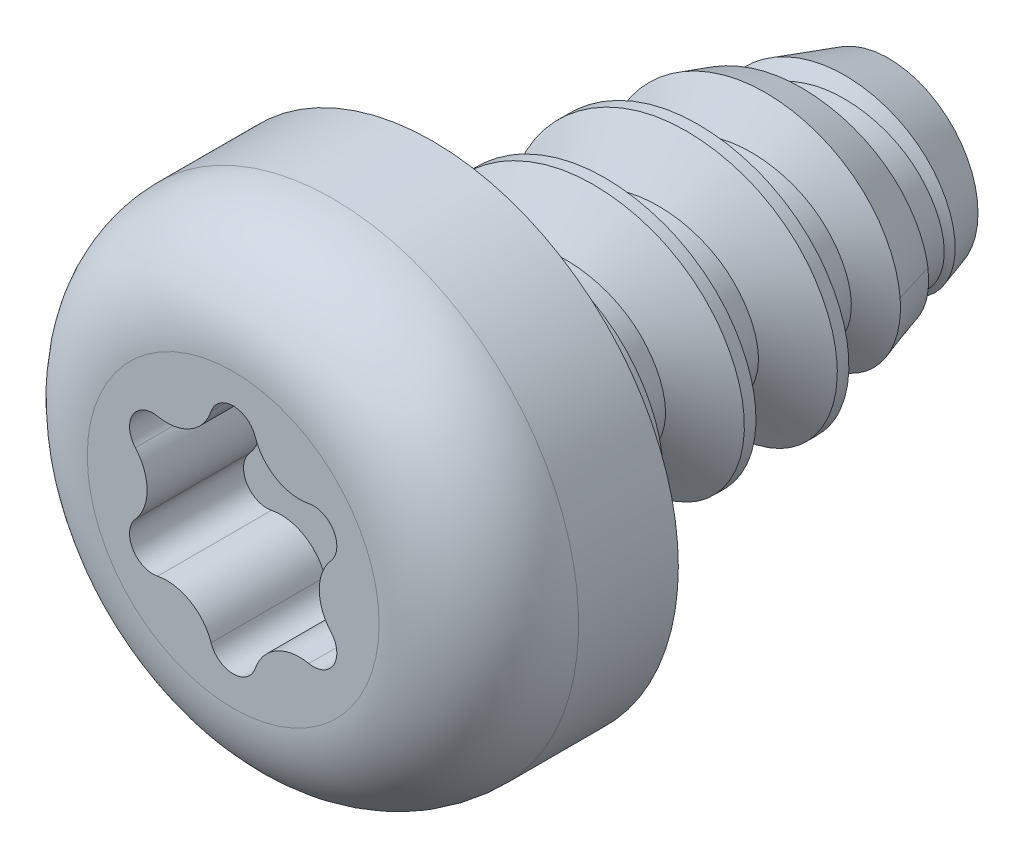
SolidWorks part; units mm, degrees
ref_plane "Front" through (0, 0, 0) normal (0, 0, 1) x (1, 0, 0)
ref_plane "Top" through (0, 0, 0) normal (0, 1, 0) x (1, 0, 0)
ref_plane "Right" through (0, 0, 0) normal (1, 0, 0) x (0, 0, -1)
sketch "HeadS" plane through (0, 0, 0) normal (0, 0, 1) x (1, 0, 0)
  circle A0 centre (0, 0) radius 4.31
extrude "Head" add sketch "HeadS" along normal blind 3.5
ref_plane "HeadTopRefP" through (0, 0, 3.5) normal (0, 0, 1) x (1, 0, 0)
sketch "HeadShapeS" plane through (0, 0, 0) normal (1, 0, 0) x (0, 0, -1)
  line L2 (-3.5, 4.31) -> (-3.5, -4.31) construction
  line L4 (0, 4.31) -> (-3.5, 4.31) construction
  line L5 (-1.75, 4.31) -> (-1.75, 4.41)
  line L6 (-1.75, 4.41) -> (-3.6, 4.41)
  line L7 (-3.6, 4.41) -> (-3.6, 2.56)
  line L8 (-3.6, 2.56) -> (-3.5, 2.56)
  line L11 (0, 0) -> (-3.5, 0) construction
  arc A0 (-3.5, 2.56) -> (-1.75, 4.31) centre (-1.75, 2.56) cw
  dimension "D1" = 0.1
  dimension "D2" = 0.1
revolve "HeadShape" cut sketch "HeadShapeS" angle 360 about L11
sketch "ThreadBodyS" plane through (0, 0, 0) normal (1, 0, 0) x (0, 0, -1)
  line L0 (0.4075, 1.6177) -> (0.9169, 2.5) construction
  line L2 (0.9169, 2.5) -> (1.1206, 2.5)
  line L3 (1.1206, 2.5) -> (1.63, 1.6177) construction
  line L4 (1.63, 1.6177) -> (0.4075, 1.6177) construction
  line L5 (1.63, 1.6177) -> (2.0375, 1.6177) construction
  line L6 (0.4075, 1.6177) -> (0, 1.6177) construction
  line L10 (0, 4.31) -> (0, -4.31) construction
  line L11 (0.9169, 2.5) -> (0.4075, 1.6177)
  line L12 (0.4075, 1.6177) -> (1.63, 1.6177)
  line L13 (1.63, 1.6177) -> (1.1206, 2.5)
  line L14 (0, 0) -> (-3.5, 0) construction
  line L15 (0, 0) -> (-3.5, 0) construction
  point P11 (1.0188, 2.5)
  dimension "D1" = 60
  dimension "D3" = 0.4075
  dimension "D4" = 0.2037
  dimension "Screw Dia" = 5
ref_plane "HeadBottomRefP" through (0, 0, -1.0188) normal (0, 0, 1) x (1, 0, 0)
sketch "ShaftS" plane through (0, 0, 0) normal (1, 0, 0) x (0, 0, -1)
  line L0 (0, 0) -> (8, 0)
  line L2 (8, -1.6177) -> (0, -1.6177) construction
  line L3 (8, 0) -> (8, 1.6177)
  line L4 (8, 1.6177) -> (0, 1.6177)
  line L5 (0, 0) -> (-3.5, 0) construction
  line L6 (0, 1.6177) -> (0, 0)
  line L7 (8, 0) -> (10.54, 0) construction
  line L8 (0.4075, 1.6177) -> (1.63, 1.6177) construction
  point P7 (0, 1.6177)
  dimension "D1" = 2.54
revolve "Shaft" add sketch "ShaftS" angle 360 about L7
sketch "ThreadProfileS" plane through (0, 0, -1.0188) normal (0, 0, 1) x (1, 0, 0)
  circle A0 centre (0, 0) radius 2.5
curve "ThreadProfile" pitch 1.63 height 2.445 radius 2.5 centre (0, 0, -1.0188) axis (0, 0, -1) start towards (0, 1, 0)
sweep "ThreadBody" add profiles "ThreadBodyS" path "ThreadProfile"
pattern_linear "TBLP" count 5 spacing 1.63 along (0, 0, -1) count 2 spacing 1.63 along (0, 0, 1) of "ThreadBody"
sketch "ThreadBottomCutS" plane through (0, 0, 0) normal (1, 0, 0) x (0, 0, -1)
  line L0 (8, 1.5677) -> (4.9691, 2.5)
  line L2 (4.9691, 2.5) -> (8, 2.5)
  line L3 (8, 2.5) -> (8, 1.5677) construction
  line L4 (8, 1.5677) -> (8, 0)
  line L5 (0, 0) -> (8, 0) construction
  line L6 (0.9169, 2.5) -> (1.1206, 2.5) construction
  line L7 (11.26, 0) -> (11.26, 2.5)
  line L8 (11.26, 2.5) -> (8, 2.5)
  line L9 (8, 0) -> (11.26, 0)
  dimension "D3" = 3.26
  dimension "D1" = 17.097
  dimension "D2" = 0.05
revolve "ThreadBottomCut" cut sketch "ThreadBottomCutS" angle 360 about L5
sketch "ScrewCutProfileS" plane through (0, 0, 3.5) normal (0, 0, 1) x (1, 0, 0)
  line L0 (0, 0) -> (0, 2.0365) construction
  line L1 (-0.7552, 1.3081) -> (0, 0)
  line L2 (0, 0) -> (0.7552, 1.3081)
  arc A0 (-0.7552, 1.3081) -> (-0.3882, 1.7571) centre (-1.1647, 2.0173) ccw
  arc A1 (-0.3882, 1.7571) -> (0.3882, 1.7571) centre (0, 1.627) cw
  arc A2 (0.3882, 1.7571) -> (0.7552, 1.3081) centre (1.1647, 2.0173) ccw
  circle A5 centre (0, 0) radius 2.0365 construction
  dimension "D2" = 0.4094
  dimension "D3" = 0.8189
  dimension "D1" = 60
ref_axis "ThreadAxis" through (0, 0, 3.5) along (0, 0, -1)
extrude "ScrewCutProfile" cut sketch "ScrewCutProfileS" against normal blind 2
pattern_circular "SCPCP" count 6 over 360 about axis through (0, 0, 3.5) along (0, 0, -1) of "ScrewCutProfile"
sketch "ThreadReferences" plane through (0, 0, 0) normal (1, 0, 0) x (0, 0, -1)
  line L0 (8, 2.5) -> (8, -2.5) construction
  point P0 (-3.5, 2.56)
  point P1 (0, 4.31)
  point P3 (4.9691, -2.5)
equation "\"D3@TBLP\" = \"Pitch@ThreadBodyS\""
equation "\"D1@TBLP\" =  ( \"Body Length@ShaftS\" / \"Pitch@ThreadBodyS\" ) "
equation "\"D1@ScrewCutProfile\" = \"Head Ht@Head\" * 2 / 3.5"
equation "\"D3@ThreadBodyS\" = \"Pitch@ThreadBodyS\" / 4"
equation "\"D4@ThreadBodyS\" = \"Pitch@ThreadBodyS\" / 8"
equation "\"D4@TBLP\" = \"D3@TBLP\""
equation "\"D4@ThreadProfile\" = \"Pitch@ThreadBodyS\""
equation "\"D2@ScrewCutProfileS\" = \"Head Dia@HeadS\" * .0475"
equation "\"D3@ScrewCutProfileS\" = \"Head Dia@HeadS\" * .095"
equation "\"M@ScrewCutProfileS\" = \"Head Dia@HeadS\" * 0.4725"
equation "\"D3@ThreadBottomCutS\" = \"D4@ThreadProfile\" * 2"
